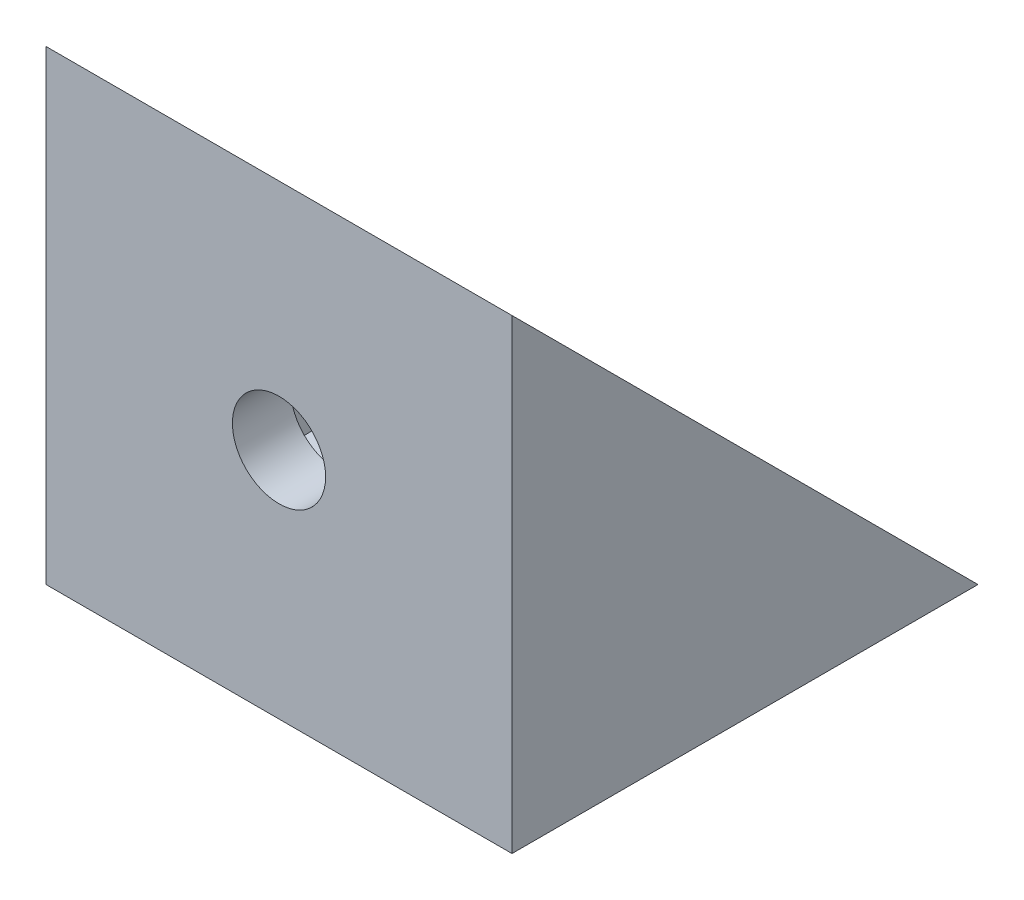
SolidWorks part; units mm, degrees
ref_plane "Ebene vorne" through (0, 0, 0) normal (0, 0, 1) x (1, 0, 0)
ref_plane "Ebene oben" through (0, 0, 0) normal (0, 1, 0) x (1, 0, 0)
ref_plane "Ebene rechts" through (0, 0, 0) normal (1, 0, 0) x (0, 0, -1)
sketch "Skizze1" plane through (0, 0, 0) normal (1, 0, 0) x (0, 0, -1)
  line L0 (0, 0) -> (0, 40)
  line L1 (0, 40) -> (40, 0)
  line L2 (40, 0) -> (0, 0)
  dimension "D1" = 40
  dimension "D2" = 40
extrude "Aufsatz-Linear austragen1" add sketch "Skizze1" along normal blind 20 and the other way blind 20
sketch "Skizze2" plane through (0, 0, 0) normal (1, 0, 0) x (0, 0, -1)
  line L0 (5, 35) -> (5, 5)
  line L1 (5, 5) -> (35, 5)
  line L2 (35, 5) -> (5, 35)
  line L3 (40, 0) -> (0, 40) construction
  line L4 (0, 40) -> (0, 0) construction
  line L5 (0, 0) -> (40, 0) construction
  dimension "D1" = 5
  dimension "D2" = 5
extrude "Schnitt-Linear austragen1" cut sketch "Skizze2" against normal blind 15 and the other way blind 15
sketch "Skizze3" plane through (0, 0, 0) normal (0, 0, 1) x (1, 0, 0)
  line L0 (0, 53.2316) -> (0, -21.655) construction
  circle A0 centre (0, 20) radius 4
  dimension "D2" = 8
  dimension "D1" = 20
extrude "Schnitt-Linear austragen2" cut sketch "Skizze3" against normal up to next
sketch "Skizze4" plane through (0, 0, 0) normal (0, -1, 0) x (1, 0, 0)
  line L0 (0, -46.3771) -> (0, 18.7831) construction
  circle A0 centre (0, -20) radius 4
  dimension "D2" = 8
  dimension "D1" = 20
extrude "Schnitt-Linear austragen3" cut sketch "Skizze4" against normal up to next
